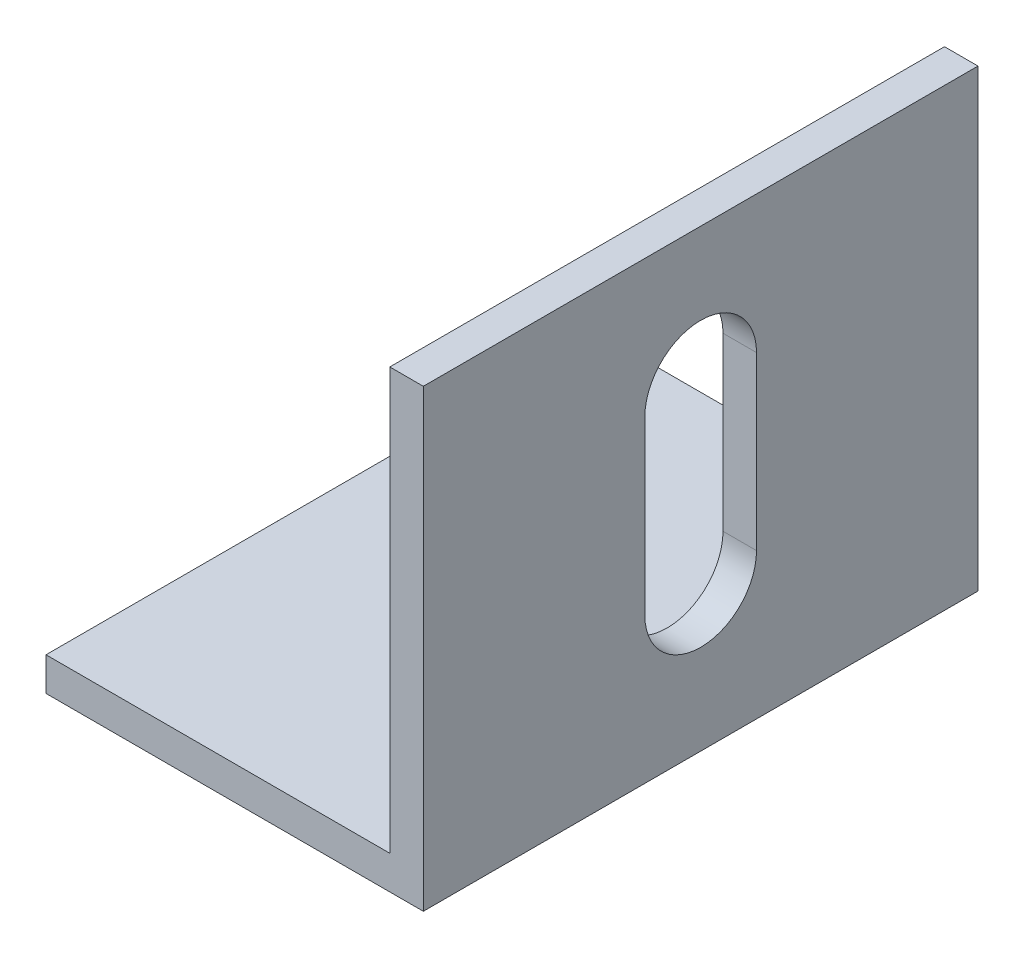
SolidWorks part; units mm, degrees
material "Galvanized Steel"
ref_plane "Front Plane" through (0, 0, 0) normal (0, 0, 1) x (1, 0, 0)
ref_plane "Top Plane" through (0, 0, 0) normal (0, 1, 0) x (1, 0, 0)
ref_plane "Right Plane" through (0, 0, 0) normal (1, 0, 0) x (0, 0, -1)
sketch "Sketch1" plane through (0, 0, 0) normal (0, 0, 1) x (1, 0, 0)
  line L0 (-15.6337, 0) -> (0, 0)
  line L2 (-15.6337, 0) -> (-15.6337, -1.524)
  line L3 (-15.6337, -1.524) -> (1.524, -1.524)
  line L6 (1.524, -1.524) -> (1.524, 19.1516)
  line L7 (1.524, 19.1516) -> (0, 19.1516)
  line L8 (0, 0) -> (0, 19.1516)
  dimension "D2" = 1.524
  dimension "D3" = 17.1577
  dimension "D4" = 20.6756
extrude "Boss-Extrude1" add sketch "Sketch1" along normal mid plane 25.2222
hole_wizard "#8 Clearance Hole1" positions "Sketch4" profile "Sketch3" hole size "#8" standard "ANSI Inch"
sketch "Sketch4" plane through (0, 0, 0) normal (0, 1, 0) x (1, 0, 0)
  line L0 (-7.8169, 12.6111) -> (-7.8168, -12.6111) construction
  line L1 (0, 12.6111) -> (-15.6337, 12.6111) construction
  line L2 (0, -12.6111) -> (-15.6337, -12.6111) construction
  line L4 (0, 0) -> (-15.6337, 0) construction
  line L5 (-15.6337, -12.6111) -> (-15.6337, 12.6111) construction
  point P0 (-7.8168, 0)
sketch "Sketch3" plane through (-7.8168, 0, 0) normal (1, 0, 0) x (0, 0, 1)
  line L0 (0, 0) -> (0, 33.1007)
  line L1 (0, 33.1007) -> (2.2479, 31.75)
  line L2 (2.2479, 31.75) -> (2.2479, 0)
  line L5 (2.2479, 0) -> (0, 0)
  line L10 (0, 33.1007) -> (-2.2479, 31.75) construction
  line L11 (0, -6.35) -> (0, 107.95) construction
  dimension "Hole Dia." = 4.4958
  dimension "Hole Depth" = 31.75
  dimension "Drill Angle" = 118
sketch "Sketch5" plane through (0, 0, 0) normal (-1, 0, 0) x (0, 0, 1)
  line L0 (0, 19.1516) -> (0, 0) construction
  line L1 (12.6111, 19.1516) -> (-12.6111, 19.1516) construction
  line L3 (0, 12.9032) -> (0, 5.1054) construction
  line L4 (2.54, 12.9032) -> (2.54, 5.1054)
  line L5 (-2.54, 12.9032) -> (-2.54, 5.1054)
  line L6 (12.6111, 0) -> (-12.6111, 0) construction
  arc A0 (2.54, 12.9032) -> (-2.54, 12.9032) centre (0, 12.9032) ccw
  arc A1 (-2.54, 5.1054) -> (2.54, 5.1054) centre (0, 5.1054) ccw
  point P8 (0, 9.0043)
  dimension "D1" = 2.54
  dimension "D2" = 6.2484
  dimension "D3" = 7.7978
extrude "Cut-Extrude1" cut sketch "Sketch5" against normal through all
